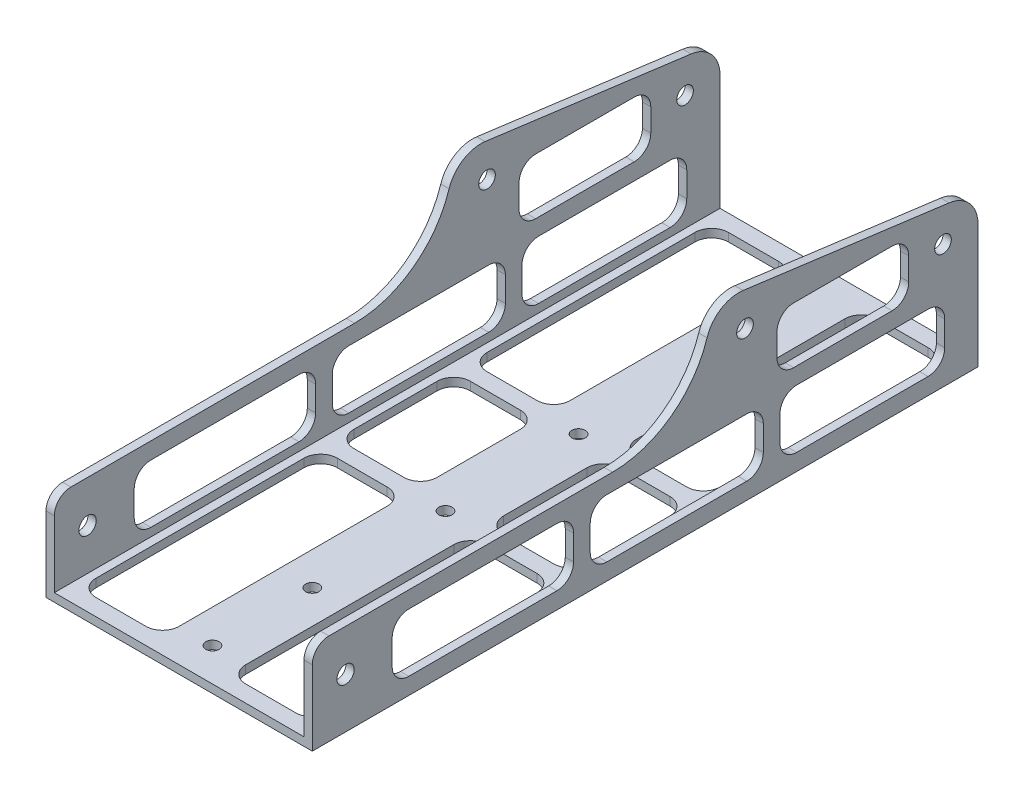
SolidWorks part; units mm, degrees
ref_plane "Front Plane" through (0, 0, 0) normal (0, 0, 1) x (1, 0, 0)
ref_plane "Top Plane" through (0, 0, 0) normal (0, 1, 0) x (1, 0, 0)
ref_plane "Right Plane" through (0, 0, 0) normal (1, 0, 0) x (0, 0, -1)
sketch "Sketch1" plane through (0, 0, 0) normal (0, 0, 1) x (1, 0, 0)
  line L0 (0, 0) -> (0, 73.025)
  line L1 (0, 73.025) -> (3.175, 73.025)
  line L2 (3.175, 73.025) -> (3.175, 3.175)
  line L3 (3.175, 3.175) -> (98.425, 3.175)
  line L4 (98.425, 3.175) -> (98.425, 73.025)
  line L5 (98.425, 73.025) -> (101.6, 73.025)
  line L6 (101.6, 73.025) -> (101.6, 0)
  line L7 (101.6, 0) -> (0, 0)
  dimension "D1" = 3.175
  dimension "D2" = 3.175
  dimension "D3" = 3.175
  dimension "D4" = 101.6
  dimension "D5" = 69.85
  dimension "D6" = 69.85
extrude "Boss-Extrude1" add sketch "Sketch1" along normal blind 254
sketch "Sketch2" plane through (101.6, 0, 0) normal (1, 0, 0) x (0, 0, -1)
  line L0 (-254, 0) -> (-254, 73.025) construction
  line L1 (-254, 0) -> (0, 0) construction
  circle A0 centre (-241.3, 19.05) radius 3.302
  circle A1 centre (-88.9, 57.15) radius 3.175
  dimension "D1" = 6.604
  dimension "D4" = 6.35
  dimension "D2" = 152.4
  dimension "D3" = 12.7
  dimension "D5" = 19.05
  dimension "D6" = 57.15
extrude "Cut-Extrude1" cut sketch "Sketch2" against normal blind 203.2
sketch "Sketch3" plane through (0, 3.175, 0) normal (0, 1, 0) x (1, 0, 0)
  line L2 (98.425, 0) -> (3.175, 0) construction
  line L4 (50.8, 0) -> (50.8, -254) construction
  line L5 (98.425, -254) -> (3.175, -254) construction
  circle A0 centre (50.8, -50.8) radius 2.54
  circle A1 centre (50.8, -101.6) radius 2.54
  circle A2 centre (50.8, -152.4) radius 2.54
  circle A3 centre (50.8, -203.2) radius 2.54
  dimension "D1" = 5.08
  dimension "D2" = 50.8
  dimension "D5" = 50.8
  dimension "D3" = 50.8
  dimension "D4" = 50.8
extrude "Cut-Extrude2" cut sketch "Sketch3" against normal blind 9.525 contours A2 | A2 | A3 | A3 | A0 | A1 region at (50.8, 3.175, 152.4) region at (50.8, 3.175, 203.2)
sketch "Sketch4" plane through (101.6, 0, 0) normal (1, 0, 0) x (0, 0, -1)
  line L1 (-254, 73.025) -> (-101.6, 73.025)
  line L2 (-254, 73.025) -> (-254, 34.925)
  line L3 (-254, 34.925) -> (-139.446, 34.925)
  line L4 (-101.6, 73.025) -> (-101.6, 72.771)
  arc A0 (-139.446, 34.925) -> (-101.6, 72.771) centre (-139.446, 72.771) ccw
  dimension "D3" = 37.846
  dimension "D1" = 38.1
  dimension "D2" = 152.4
extrude "Cut-Extrude3" cut sketch "Sketch4" against normal through all
sketch "Sketch5" plane through (0, 0, 0) normal (-1, 0, 0) x (0, 0, 1)
  line L0 (88.9, 57.15) -> (13.3519, 47.2039) construction
  line L1 (88.9, 57.15) -> (0, 57.15) construction
  line L2 (0, 73.025) -> (0, 0) construction
  circle A0 centre (88.9, 57.15) radius 3.175 construction
  circle A3 centre (88.9, 57.15) radius 3.175
  circle A4 centre (13.3519, 47.2039) radius 3.175
  dimension "D3" = 7.5
  dimension "D2" = 76.2
extrude "Cut-Extrude4" cut sketch "Sketch5" against normal through all contours A4 region at (0, 47.2039, 13.3519)
sketch "Sketch6" plane through (0, 0, 0) normal (-1, 0, 0) x (0, 0, 1)
  line L0 (13.3519, 47.2039) -> (88.9, 57.15) construction
  line L1 (11.6942, 59.7953) -> (117.2593, 73.6932)
  line L2 (11.6942, 59.7953) -> (-12.4817, 56.6124)
  line L3 (-12.4817, 56.6124) -> (-7.0221, 78.936)
  line L4 (-7.0221, 78.936) -> (117.2593, 83.6489)
  line L5 (117.2593, 83.6489) -> (117.2593, 62.8772)
  line L6 (11.6942, 59.7953) -> (87.2423, 69.7413) construction
  arc M4 (139.446, 34.925) -> (101.6, 72.771) centre (139.446, 72.771) cw
  line M5 (101.6, 72.771) -> (101.6, 73.025)
  line M6 (101.6, 73.025) -> (0, 73.025)
  line M7 (0, 73.025) -> (0, 0)
  dimension "D1" = 12.7
extrude "Cut-Extrude6" cut sketch "Sketch6" against normal through all contours L5 L4 L3 L2 L1 M7 M6 M5 M4 | L2 L1 M4 M5 M6 M7 region at (0, 68.0619, 36.7869) region at (0, 75.5509, 52.0208)
fillet "Fillet1" radius 12.7 4 edges at (100.0125, 58.2557, 0) (1.5875, 58.2557, 0) (100.0125, 71.6338, 101.6171) (1.5875, 71.6338, 101.6171)
fillet "Fillet2" radius 6.35 2 edges at (100.0125, 34.925, 254) (1.5875, 34.925, 254)
sketch "Sketch7" plane through (0, 0, 0) normal (-1, 0, 0) x (0, 0, 1)
  line L0 (19.05, 6.35) -> (69.215, 6.35)
  line L1 (12.7, 12.7) -> (12.7, 22.225)
  line L2 (217.17, 28.575) -> (160.655, 28.575)
  line L3 (223.52, 22.225) -> (223.52, 12.7)
  line L4 (70.3422, 56.2887) -> (32.7762, 56.2887)
  line L5 (254, 0) -> (254, 28.575)
  line L6 (247.65, 34.925) -> (139.446, 34.925)
  line L7 (89.6162, 70.0539) -> (11.0423, 59.7094)
  line L8 (0, 47.1181) -> (0, 0)
  line L9 (0, 0) -> (254, 0)
  line L10 (254, 0) -> (254, 28.575)
  line L11 (247.65, 34.925) -> (139.446, 34.925)
  line L12 (89.6162, 70.0539) -> (11.0423, 59.7094)
  line L13 (0, 47.1181) -> (0, 0)
  line L14 (0, 0) -> (254, 0)
  line L15 (70.3422, 34.925) -> (32.7762, 34.925)
  line L16 (26.4262, 49.9387) -> (26.4262, 41.275)
  line L17 (76.6922, 49.9387) -> (76.6922, 41.275)
  line L18 (88.265, 6.35) -> (141.605, 6.35)
  line L20 (160.655, 6.35) -> (217.17, 6.35)
  line L21 (223.52, 34.925) -> (6.35, 34.925) construction
  line L22 (75.565, 22.225) -> (75.565, 12.7)
  line L23 (147.955, 22.225) -> (147.955, 12.7)
  line L24 (81.915, 22.225) -> (81.915, 12.7)
  line L25 (154.305, 22.225) -> (154.305, 12.7)
  line L26 (69.215, 28.575) -> (19.05, 28.575)
  line L27 (141.605, 28.575) -> (88.265, 28.575)
  line L28 (223.52, 28.575) -> (6.35, 28.575) construction
  circle A0 centre (13.3519, 47.2039) radius 3.175 construction
  circle A1 centre (13.3519, 47.2039) radius 3.175
  circle A2 centre (88.9, 57.15) radius 3.175 construction
  circle A3 centre (88.9, 57.15) radius 3.175
  arc A4 (254, 28.575) -> (247.65, 34.925) centre (247.65, 28.575) ccw
  arc A5 (103.3775, 61.3089) -> (139.446, 34.925) centre (139.446, 72.771) ccw
  arc A6 (103.3775, 61.3089) -> (89.6162, 70.0539) centre (91.2739, 57.4625) ccw
  arc A7 (11.0423, 59.7094) -> (0, 47.1181) centre (12.7, 47.1181) ccw
  arc A8 (254, 28.575) -> (247.65, 34.925) centre (247.65, 28.575) ccw
  arc A9 (103.3775, 61.3089) -> (139.446, 34.925) centre (139.446, 72.771) ccw
  arc A10 (103.3775, 61.3089) -> (89.6162, 70.0539) centre (91.2739, 57.4625) ccw
  arc A11 (11.0423, 59.7094) -> (0, 47.1181) centre (12.7, 47.1181) ccw
  circle A12 centre (13.3519, 47.2039) radius 12.7
  circle A13 centre (88.9, 57.15) radius 12.7
  circle A14 centre (241.3, 19.05) radius 12.7
  arc A15 (70.3422, 34.925) -> (76.6922, 41.275) centre (70.3422, 41.275) ccw
  arc A16 (76.6922, 49.9387) -> (70.3422, 56.2887) centre (70.3422, 49.9387) ccw
  arc A17 (26.4262, 49.9387) -> (32.7762, 56.2887) centre (32.7762, 49.9387) cw
  arc A18 (26.4262, 41.275) -> (32.7762, 34.925) centre (32.7762, 41.275) ccw
  arc A19 (217.17, 6.35) -> (223.52, 12.7) centre (217.17, 12.7) ccw
  arc A20 (217.17, 28.575) -> (223.52, 22.225) centre (217.17, 22.225) cw
  arc A21 (154.305, 22.225) -> (160.655, 28.575) centre (160.655, 22.225) cw
  arc A22 (154.305, 12.7) -> (160.655, 6.35) centre (160.655, 12.7) ccw
  arc A23 (147.955, 12.7) -> (141.605, 6.35) centre (141.605, 12.7) cw
  arc A24 (147.955, 22.225) -> (141.605, 28.575) centre (141.605, 22.225) ccw
  arc A25 (81.915, 22.225) -> (88.265, 28.575) centre (88.265, 22.225) cw
  arc A26 (81.915, 12.7) -> (88.265, 6.35) centre (88.265, 12.7) ccw
  arc A27 (19.05, 6.35) -> (12.7, 12.7) centre (19.05, 12.7) cw
  arc A28 (69.215, 6.35) -> (75.565, 12.7) centre (69.215, 12.7) ccw
  arc A29 (75.565, 22.225) -> (69.215, 28.575) centre (69.215, 22.225) ccw
  arc A30 (19.05, 28.575) -> (12.7, 22.225) centre (19.05, 22.225) ccw
  point P24 (91.1239, 58.6021)
  point P29 (12.55, 48.2577)
  point P47 (223.52, 6.35)
  point P73 (12.7, 6.35)
  dimension "D2" = 6.35
  dimension "D3" = 6.35
  dimension "D7" = 6.35
  dimension "D8" = 6.35
  dimension "D9" = 6.35
  dimension "D4" = 12.7
  dimension "8" = 210.82
  dimension "D1" = 0
  dimension "D6" = 6.35
extrude "Cut-Extrude7" cut sketch "Sketch7" against normal through all contours L16 A18 L15 A15 L17 A16 L4 A17 | L26 A30 L1 A27 L0 A28 L22 A29 | L24 A26 L18 A23 L23 A24 L27 A25 | L25 A22 L20 A19 L3 A20 L2 A21 region at (0, 17.4625, 44.1325) region at (0, 17.4625, 188.9125) region at (0, 45.6068, 51.5592) region at (0, 17.4625, 114.935)
sketch "Sketch8" plane through (0, 0, 0) normal (0, -1, 0) x (1, 0, 0)
  line L0 (12.7, 6.35) -> (31.75, 6.35)
  line L1 (95.25, 6.35) -> (95.25, 247.65)
  line L2 (95.25, 247.65) -> (50.8, 247.65)
  line L3 (6.35, 241.3) -> (6.35, 212.725)
  line L4 (0, 0) -> (101.6, 0)
  line L5 (101.6, 0) -> (101.6, 254)
  line L6 (101.6, 254) -> (0, 254)
  line L7 (0, 254) -> (0, 0)
  line L8 (0, 0) -> (101.6, 0)
  line L9 (101.6, 0) -> (101.6, 254)
  line L10 (101.6, 254) -> (0, 254)
  line L11 (0, 254) -> (0, 0)
  line L12 (38.1, 241.3) -> (38.1, 212.725)
  line L13 (50.8, 247.65) -> (50.8, 6.35) construction
  line L14 (50.8, 203.2) -> (38.1, 203.2)
  line L15 (50.8, 152.4) -> (38.1, 152.4)
  line L16 (50.8, 101.6) -> (38.1, 101.6)
  line L17 (50.8, 50.8) -> (38.1, 50.8)
  line L18 (31.75, 206.375) -> (12.7, 206.375)
  line L19 (50.8, 155.575) -> (38.5033, 155.575)
  line L20 (50.8, 104.775) -> (38.5033, 104.775)
  line L21 (50.8, 53.975) -> (38.5033, 53.975)
  line L22 (50.8, 200.025) -> (38.5033, 200.025)
  line L23 (50.8, 149.225) -> (38.5033, 149.225)
  line L24 (50.8, 98.425) -> (38.5033, 98.425)
  line L25 (50.8, 47.625) -> (38.5033, 47.625)
  line L26 (38.1, 193.675) -> (38.1, 161.925)
  line L27 (6.35, 193.675) -> (6.35, 161.925)
  line L28 (50.8, 203.2) -> (6.35, 203.2) construction
  line L29 (31.75, 200.025) -> (12.7, 200.025)
  line L30 (6.35, 247.65) -> (6.35, 6.35) construction
  line L31 (50.8, 206.375) -> (6.35, 206.375) construction
  line L32 (31.75, 247.65) -> (12.7, 247.65)
  line L33 (50.8, 200.025) -> (6.35, 200.025) construction
  line L34 (31.75, 155.575) -> (12.7, 155.575)
  line L35 (95.25, 247.65) -> (6.35, 247.65) construction
  line L36 (38.1, 142.875) -> (38.1, 111.125)
  line L37 (50.8, 155.575) -> (6.35, 155.575) construction
  line L38 (6.35, 142.875) -> (6.35, 111.125)
  line L39 (31.75, 149.225) -> (12.7, 149.225)
  line L40 (50.8, 152.4) -> (6.35, 152.4) construction
  line L41 (31.75, 104.775) -> (12.7, 104.775)
  line L42 (50.8, 149.225) -> (6.35, 149.225) construction
  line L43 (38.1, 92.075) -> (38.1, 60.325)
  line L44 (50.8, 104.775) -> (6.35, 104.775) construction
  line L45 (6.35, 92.075) -> (6.35, 60.325)
  line L46 (31.75, 98.425) -> (12.7, 98.425)
  line L47 (50.8, 101.6) -> (6.35, 101.6) construction
  line L48 (6.35, 41.275) -> (6.35, 12.7)
  line L49 (50.8, 98.425) -> (6.35, 98.425) construction
  line L50 (38.1, 41.275) -> (38.1, 12.7)
  line L51 (50.8, 50.8) -> (6.35, 50.8) construction
  line L52 (31.75, 53.975) -> (12.7, 53.975)
  line L53 (31.75, 47.625) -> (12.7, 47.625)
  line L54 (50.8, 53.975) -> (6.35, 53.975) construction
  line L55 (50.8, 6.35) -> (95.25, 6.35)
  line L56 (50.8, 47.625) -> (6.35, 47.625) construction
  line L57 (95.25, 41.275) -> (95.25, 12.7)
  line L58 (6.35, 6.35) -> (95.25, 6.35) construction
  line L59 (69.85, 47.625) -> (88.9, 47.625)
  line L60 (63.5, 41.275) -> (63.5, 12.7)
  line L61 (88.9, 6.35) -> (69.85, 6.35)
  line L62 (69.85, 98.425) -> (88.9, 98.425)
  line L63 (63.5, 92.075) -> (63.5, 60.325)
  line L64 (69.85, 53.975) -> (88.9, 53.975)
  line L65 (95.25, 92.075) -> (95.25, 60.325)
  line L66 (69.85, 149.225) -> (88.9, 149.225)
  line L67 (63.5, 142.875) -> (63.5, 111.125)
  line L68 (69.85, 104.775) -> (88.9, 104.775)
  line L69 (95.25, 142.875) -> (95.25, 111.125)
  line L70 (69.85, 200.025) -> (88.9, 200.025)
  line L71 (63.5, 193.675) -> (63.5, 161.925)
  line L72 (69.85, 155.575) -> (88.9, 155.575)
  line L73 (95.25, 193.675) -> (95.25, 161.925)
  line L74 (69.85, 247.65) -> (88.9, 247.65)
  line L75 (63.5, 241.3) -> (63.5, 212.725)
  line L76 (69.85, 206.375) -> (88.9, 206.375)
  line L77 (95.25, 241.3) -> (95.25, 212.725)
  line L78 (6.35, 212.725) -> (6.35, 193.675)
  line L79 (38.1, 193.675) -> (38.1, 212.725)
  line L80 (6.35, 60.325) -> (6.35, 41.275)
  line L81 (38.1, 41.275) -> (38.1, 60.325)
  line L82 (63.5, 212.725) -> (63.5, 193.675)
  line L83 (95.25, 193.675) -> (95.25, 212.725)
  line L84 (63.5, 60.325) -> (63.5, 41.275)
  line L85 (95.25, 41.275) -> (95.25, 60.325)
  circle A0 centre (50.8, 203.2) radius 12.7
  circle A1 centre (50.8, 50.8) radius 2.54
  circle A2 centre (50.8, 50.8) radius 2.54
  circle A3 centre (50.8, 101.6) radius 2.54
  circle A4 centre (50.8, 101.6) radius 2.54
  circle A5 centre (50.8, 152.4) radius 2.54
  circle A6 centre (50.8, 152.4) radius 2.54
  circle A7 centre (50.8, 203.2) radius 2.54
  circle A8 centre (50.8, 203.2) radius 2.54
  circle A9 centre (50.8, 152.4) radius 12.7
  circle A10 centre (50.8, 101.6) radius 12.7
  circle A11 centre (50.8, 50.8) radius 12.7
  arc A12 (12.7, 6.35) -> (6.35, 12.7) centre (12.7, 12.7) cw
  arc A13 (38.1, 12.7) -> (31.75, 6.35) centre (31.75, 12.7) cw
  arc A14 (38.1, 41.275) -> (31.75, 47.625) centre (31.75, 41.275) ccw
  arc A15 (12.7, 47.625) -> (6.35, 41.275) centre (12.7, 41.275) ccw
  arc A16 (38.1, 92.075) -> (31.75, 98.425) centre (31.75, 92.075) ccw
  arc A17 (12.7, 98.425) -> (6.35, 92.075) centre (12.7, 92.075) ccw
  arc A18 (6.35, 111.125) -> (12.7, 104.775) centre (12.7, 111.125) ccw
  arc A19 (31.75, 104.775) -> (38.1, 111.125) centre (31.75, 111.125) ccw
  arc A20 (38.1, 142.875) -> (31.75, 149.225) centre (31.75, 142.875) ccw
  arc A21 (12.7, 149.225) -> (6.35, 142.875) centre (12.7, 142.875) ccw
  arc A22 (6.35, 161.925) -> (12.7, 155.575) centre (12.7, 161.925) ccw
  arc A23 (31.75, 155.575) -> (38.1, 161.925) centre (31.75, 161.925) ccw
  arc A24 (38.1, 193.675) -> (31.75, 200.025) centre (31.75, 193.675) ccw
  arc A25 (12.7, 200.025) -> (6.35, 193.675) centre (12.7, 193.675) ccw
  arc A26 (12.7, 206.375) -> (6.35, 212.725) centre (12.7, 212.725) cw
  arc A27 (38.1, 212.725) -> (31.75, 206.375) centre (31.75, 212.725) cw
  arc A28 (38.1, 241.3) -> (31.75, 247.65) centre (31.75, 241.3) ccw
  arc A29 (12.7, 247.65) -> (6.35, 241.3) centre (12.7, 241.3) ccw
  arc A30 (12.7, 53.975) -> (6.35, 60.325) centre (12.7, 60.325) cw
  arc A31 (38.1, 60.325) -> (31.75, 53.975) centre (31.75, 60.325) cw
  arc A32 (88.9, 47.625) -> (95.25, 41.275) centre (88.9, 41.275) cw
  arc A33 (63.5, 41.275) -> (69.85, 47.625) centre (69.85, 41.275) cw
  arc A34 (88.9, 6.35) -> (95.25, 12.7) centre (88.9, 12.7) ccw
  arc A35 (63.5, 12.7) -> (69.85, 6.35) centre (69.85, 12.7) ccw
  arc A36 (63.5, 92.075) -> (69.85, 98.425) centre (69.85, 92.075) cw
  arc A37 (63.5, 60.325) -> (69.85, 53.975) centre (69.85, 60.325) ccw
  arc A38 (88.9, 98.425) -> (95.25, 92.075) centre (88.9, 92.075) cw
  arc A39 (88.9, 53.975) -> (95.25, 60.325) centre (88.9, 60.325) ccw
  arc A40 (63.5, 142.875) -> (69.85, 149.225) centre (69.85, 142.875) cw
  arc A41 (69.85, 104.775) -> (63.5, 111.125) centre (69.85, 111.125) cw
  arc A42 (95.25, 111.125) -> (88.9, 104.775) centre (88.9, 111.125) cw
  arc A43 (88.9, 149.225) -> (95.25, 142.875) centre (88.9, 142.875) cw
  arc A44 (63.5, 193.675) -> (69.85, 200.025) centre (69.85, 193.675) cw
  arc A45 (69.85, 155.575) -> (63.5, 161.925) centre (69.85, 161.925) cw
  arc A46 (95.25, 161.925) -> (88.9, 155.575) centre (88.9, 161.925) cw
  arc A47 (88.9, 200.025) -> (95.25, 193.675) centre (88.9, 193.675) cw
  arc A48 (63.5, 241.3) -> (69.85, 247.65) centre (69.85, 241.3) cw
  arc A49 (63.5, 212.725) -> (69.85, 206.375) centre (69.85, 212.725) ccw
  arc A50 (88.9, 206.375) -> (95.25, 212.725) centre (88.9, 212.725) ccw
  arc A51 (88.9, 247.65) -> (95.25, 241.3) centre (88.9, 241.3) cw
  point P74 (38.1, 47.625)
  point P80 (38.1, 98.425)
  point P91 (38.1, 149.225)
  point P102 (38.1, 200.025)
  point P113 (38.1, 247.65)
  point P122 (38.1, 53.975)
  dimension "D6" = 6.35
  dimension "1" = 25.4
  dimension "D9" = 6.35
  dimension "D10" = 6.35
  dimension "D7" = 3.175
  dimension "D1" = 0
  dimension "D2" = 0
  dimension "D3" = 0
  dimension "D4" = 0
  dimension "D5" = 0
  dimension "D8" = 3.175
extrude "Cut-Extrude8" cut sketch "Sketch8" against normal blind 116.332 contours L32 A29 L3 A26 L18 A27 L12 A28 | A51 L2 A48 L75 A49 L76 A50 L1 | L29 A25 L27 A22 L34 A23 L26 A24 | A47 L70 A44 L71 A45 L72 A46 L1 | L39 A21 L38 A18 L41 A19 L36 A20 | A43 L66 A40 L67 A41 L68 A42 L1 | A31 L43 A16 L46 A17 L45 A30 L52 | L64 A39 L1 A38 L62 A36 L63 A37 | L53 A15 L48 A12 L0 A13 L50 A14 | L60 A35 L55 A34 L1 A32 L59 A33 | L79 A27 L18 A26 L78 A25 L29 A24 | L81 A31 L52 A30 L80 A15 L53 A14 | A50 L76 A49 L82 A44 L70 A47 L1 | A39 L64 A37 L84 A33 L59 A32 L1 region at (22.225, 0, 26.9875) region at (22.225, 0, 203.2) region at (79.375, 0, 177.8) region at (79.375, 0, 127) region at (79.375, 0, 50.8) region at (22.225, 0, 50.8) region at (22.225, 0, 76.2) region at (79.375, 0, 76.2) region at (79.375, 0, 26.9875) region at (79.375, 0, 203.2) region at (79.375, 0, 227.0125) region at (22.225, 0, 177.8) region at (22.225, 0, 227.0125) region at (22.225, 0, 127)
sketch "Sketch9" plane through (0, 3.175, 0) normal (0, 1, 0) x (1, 0, 0)
  line L1 (98.425, -254) -> (3.175, -254) construction
  line L2 (38.1, -241.3) -> (38.1, -161.925) construction
  circle A0 centre (50.8, -241.3) radius 2.54
  point P4 (50.8, -254)
  dimension "D1" = 5.08
  dimension "D2" = 12.7
  dimension "D3" = 12.7
extrude "Cut-Extrude9" cut sketch "Sketch9" against normal up to next contours A0
